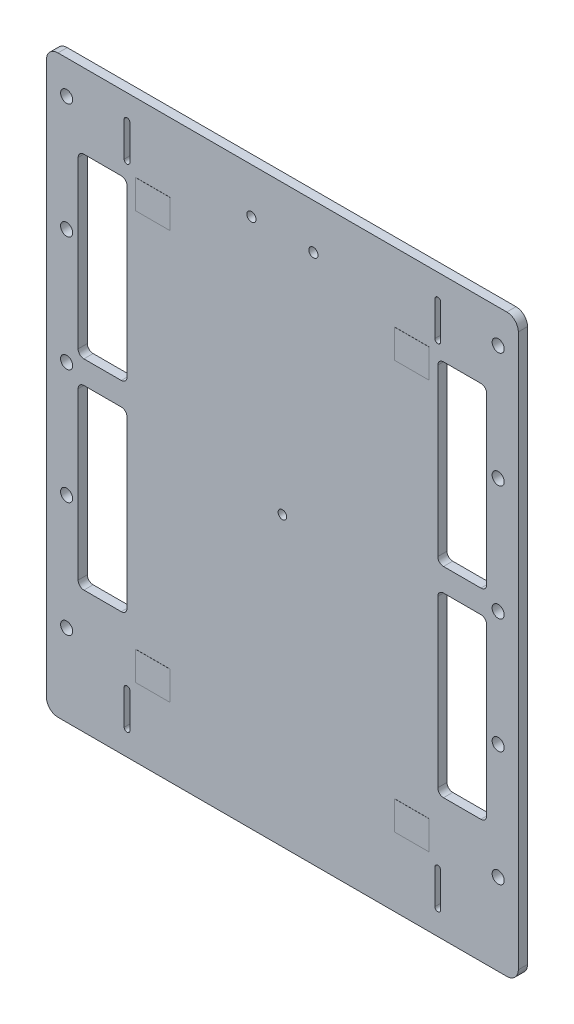
SolidWorks part; units mm, degrees
material "Oshpark board"
ref_plane "Front Plane" through (0, 0, 0) normal (0, 0, 1) x (1, 0, 0)
ref_plane "Top Plane" through (0, 0, 0) normal (0, 1, 0) x (1, 0, 0)
ref_plane "Right Plane" through (0, 0, 0) normal (1, 0, 0) x (0, 0, -1)
sketch "Sketch1" plane through (0, 0, 0) normal (0, 0, 1) x (1, 0, 0)
  line L1 (-39, -50) -> (39, -50)
  line L2 (-41, -48) -> (-41, 48)
  line L3 (-39, 50) -> (39, 50)
  line L4 (41, -48) -> (41, 48)
  line L5 (-41, -50) -> (41, 50) construction
  line L6 (-41, 50) -> (41, -50) construction
  arc A0 (-39, -50) -> (-41, -48) centre (-39, -48) cw
  arc A1 (39, -50) -> (41, -48) centre (39, -48) ccw
  arc A2 (39, 50) -> (41, 48) centre (39, 48) cw
  arc A3 (-41, 48) -> (-39, 50) centre (-39, 48) cw
  point P0 (0, 0)
  dimension "D3" = 2
  dimension "D1" = 100
  dimension "D2" = 82
extrude "Boss-Extrude1" add sketch "Sketch1" along normal blind 1.6
sketch "Sketch2" plane through (0, 0, 1.6) normal (0, 0, 1) x (1, 0, 0)
  line L0 (39, 50) -> (-39, 50) construction
  line L1 (-41, 48) -> (-41, -48) construction
  line L3 (-37.5, 44.2) -> (-37.5, 4.2) construction
  circle A0 centre (0, 0) radius 0.75
  circle A1 centre (-37.5, 44.2) radius 1.05
  circle A2 centre (37.5, 44.2) radius 1.05
  circle A3 centre (37.5, 4.2) radius 1.05
  circle A4 centre (37.5, -35.8) radius 1.05
  circle A5 centre (-37.5, 4.2) radius 1.05
  circle A6 centre (-37.5, -35.8) radius 1.05
  circle A7 centre (-5.38, 42.15) radius 0.8
  circle A8 centre (5.39, 42.15) radius 0.8
  dimension "D1" = 1.5
  dimension "D2" = 2.1
  dimension "D9" = 10.77
  dimension "D7" = 1.6
  dimension "D11" = 7.85
  dimension "D12" = 35.62
  dimension "D3" = 5.8
  dimension "D4" = 3.5
  dimension "D8" = 40
  dimension "D10" = 37.5
  dimension "D5" = 2
  dimension "D6" = 3
extrude "Cut-Extrude1" cut sketch "Sketch2" against normal through all
sketch "Sketch3" plane through (0, 0, 1.6) normal (0, 0, 1) x (1, 0, 0)
  line L0 (39, 50) -> (-39, 50) construction
  line L1 (-34.5, 37) -> (-28, 37)
  line L2 (-35.5, 36) -> (-35.5, 7.2)
  line L3 (-34.5, 6.2) -> (-28, 6.2)
  line L4 (-27, 36) -> (-27, 7.2)
  line L5 (-41, 48) -> (-41, -48) construction
  line L6 (28, 37) -> (34.5, 37)
  line L7 (27, 36) -> (27, 7.2)
  line L8 (35.5, 36) -> (35.5, 7.2)
  line L9 (28, 6.2) -> (34.5, 6.2)
  line L10 (28, 2.2) -> (34.5, 2.2)
  line L11 (27, 1.2) -> (27, -27.6)
  line L12 (35.5, 1.2) -> (35.5, -27.6)
  line L13 (28, -28.6) -> (34.5, -28.6)
  line L14 (-34.5, 2.2) -> (-28, 2.2)
  line L15 (-35.5, 1.2) -> (-35.5, -27.6)
  line L16 (-27, 1.2) -> (-27, -27.6)
  line L17 (-34.5, -28.6) -> (-28, -28.6)
  line L18 (-34.5, 37) -> (28, 37) construction
  line L19 (-39, -50) -> (39, -50) construction
  arc A0 (-35.5, 7.2) -> (-34.5, 6.2) centre (-34.5, 7.2) ccw
  arc A1 (-28, 6.2) -> (-27, 7.2) centre (-28, 7.2) ccw
  arc A2 (-28, 37) -> (-27, 36) centre (-28, 36) cw
  arc A3 (-34.5, 37) -> (-35.5, 36) centre (-34.5, 36) ccw
  arc A4 (28, 37) -> (27, 36) centre (28, 36) ccw
  arc A5 (34.5, 37) -> (35.5, 36) centre (34.5, 36) cw
  arc A6 (27, 7.2) -> (28, 6.2) centre (28, 7.2) ccw
  arc A7 (34.5, 6.2) -> (35.5, 7.2) centre (34.5, 7.2) ccw
  arc A8 (28, 2.2) -> (27, 1.2) centre (28, 1.2) ccw
  arc A9 (34.5, 2.2) -> (35.5, 1.2) centre (34.5, 1.2) cw
  arc A10 (27, -27.6) -> (28, -28.6) centre (28, -27.6) ccw
  arc A11 (34.5, -28.6) -> (35.5, -27.6) centre (34.5, -27.6) ccw
  arc A12 (-34.5, 2.2) -> (-35.5, 1.2) centre (-34.5, 1.2) ccw
  arc A13 (-28, 2.2) -> (-27, 1.2) centre (-28, 1.2) cw
  arc A14 (-35.5, -27.6) -> (-34.5, -28.6) centre (-34.5, -27.6) ccw
  arc A15 (-28, -28.6) -> (-27, -27.6) centre (-28, -27.6) ccw
  point P12 (-27, 6.2)
  point P15 (-27, 37)
  point P18 (-35.5, 37)
  dimension "D5" = 1
  dimension "D10" = 27
  dimension "D1" = 8.5
  dimension "D2" = 30.8
  dimension "D3" = 13
  dimension "D4" = 5.5
  dimension "D8" = 62.5
  dimension "D9" = 4
  dimension "D11" = 21.4
  dimension "D6" = 2
  dimension "D7" = 2
extrude "Cut-Extrude2" cut sketch "Sketch3" against normal through all
sketch "Sketch4" plane through (0, 0, 1.6) normal (0, 0, 1) x (1, 0, 0)
  line L0 (-27, 39.75) -> (-27, 45.75) construction
  line L1 (-27.5, 39.75) -> (-27.5, 45.75)
  line L2 (-26.5, 39.75) -> (-26.5, 45.75)
  line L3 (39, 50) -> (-39, 50) construction
  line L4 (-41, 48) -> (-41, -48) construction
  line L5 (27, 39.75) -> (27, 45.75) construction
  line L6 (26.5, 39.75) -> (26.5, 45.75)
  line L7 (27.5, 39.75) -> (27.5, 45.75)
  line L8 (27, -45.75) -> (27, -39.75) construction
  line L9 (26.5, -45.75) -> (26.5, -39.75)
  line L10 (27.5, -45.75) -> (27.5, -39.75)
  line L11 (-27, -45.75) -> (-27, -39.75) construction
  line L12 (-27.5, -45.75) -> (-27.5, -39.75)
  line L13 (-26.5, -45.75) -> (-26.5, -39.75)
  line L14 (-27, 39.75) -> (27, 39.75) construction
  line L15 (-39, -50) -> (39, -50) construction
  arc A0 (-27.5, 39.75) -> (-26.5, 39.75) centre (-27, 39.75) ccw
  arc A1 (-26.5, 45.75) -> (-27.5, 45.75) centre (-27, 45.75) ccw
  arc A2 (26.5, 39.75) -> (27.5, 39.75) centre (27, 39.75) ccw
  arc A3 (27.5, 45.75) -> (26.5, 45.75) centre (27, 45.75) ccw
  arc A4 (26.5, -45.75) -> (27.5, -45.75) centre (27, -45.75) ccw
  arc A5 (27.5, -39.75) -> (26.5, -39.75) centre (27, -39.75) ccw
  arc A6 (-27.5, -45.75) -> (-26.5, -45.75) centre (-27, -45.75) ccw
  arc A7 (-26.5, -39.75) -> (-27.5, -39.75) centre (-27, -39.75) ccw
  point P2 (-27, 42.75)
  point P16 (27, 42.75)
  point P23 (27, -42.75)
  point P30 (-27, -42.75)
  dimension "D1" = 4.25
  dimension "D2" = 13.5
  dimension "D3" = 1
  dimension "D4" = 6
  dimension "D7" = 54
  dimension "D8" = 14
  dimension "D9" = 4.25
  dimension "D10" = 4.25
  dimension "D5" = 2
  dimension "D6" = 2
extrude "Cut-Extrude3" cut sketch "Sketch4" against normal blind 1.6
sketch "Sketch5" plane through (0, 0, 1.6) normal (0, 0, 1) x (1, 0, 0)
  line L0 (-41, 48) -> (-41, -48) construction
  line L1 (-25.5, 38) -> (-19.5, 38)
  line L2 (-25.5, 38) -> (-25.5, 33)
  line L3 (-25.5, 33) -> (-19.5, 33)
  line L4 (-19.5, 38) -> (-19.5, 33)
  line L5 (39, 50) -> (-39, 50) construction
  line L6 (19.5, 38) -> (19.5, 33)
  line L7 (25.5, 38) -> (25.5, 33)
  line L8 (19.5, 33) -> (25.5, 33)
  line L9 (19.5, 38) -> (25.5, 38)
  line L10 (19.5, -33) -> (19.5, -38)
  line L11 (25.5, -33) -> (25.5, -38)
  line L12 (19.5, -38) -> (25.5, -38)
  line L13 (19.5, -33) -> (25.5, -33)
  line L14 (-25.5, -33) -> (-25.5, -38)
  line L15 (-19.5, -33) -> (-19.5, -38)
  line L16 (-25.5, -38) -> (-19.5, -38)
  line L17 (-25.5, -33) -> (-19.5, -33)
  line L18 (-25.5, 38) -> (19.5, 38) construction
  line L19 (-25.5, 38) -> (-25.5, -33) construction
  dimension "D1" = 5
  dimension "D2" = 6
  dimension "D3" = 15.5
  dimension "D4" = 12
  dimension "D7" = 45
  dimension "D8" = 71
  dimension "D5" = 2
  dimension "D6" = 2
extrude "Boss-Extrude2" add sketch "Sketch5" along normal blind 0.02
hole_wizard "M2 Clearance Hole1" positions "Sketch6" profile "Sketch7" hole size "M2" standard "ANSI Metric" end condition through all
sketch "Sketch6" plane through (0, 0, 0) normal (0, 0, -1) x (-1, 0, 0)
  line L0 (-37.5, 44.2) -> (-37.5, 4.2) construction
  line L2 (-37.5, 4.2) -> (37.5, 4.2) construction
  line L4 (0, 4.2) -> (0, 34.4116) construction
  point P0 (-37.5, 24.2)
  point P26 (0, 0)
  point P27 (-37.5, -15.8)
  point P28 (0, 0)
  point P29 (0, 0)
  point P30 (0, 0)
  point P31 (0, 0)
  point P32 (37.5, -15.8)
  point P33 (37.5, 24.2)
sketch "Sketch7" plane through (37.5, 24.2, 0) normal (1, 0, 0) x (0, 1, 0)
  line L0 (0, 0) -> (0, 1.62)
  line L1 (0, 1.62) -> (1.05, 1.62)
  line L2 (1.05, 1.62) -> (1.05, 0)
  line L5 (1.05, 0) -> (0, 0)
  line L11 (0, -6.35) -> (0, 107.95) construction
  dimension "Thru Hole Dia." = 2.1
  dimension "Thru Hole Depth" = 1.62
